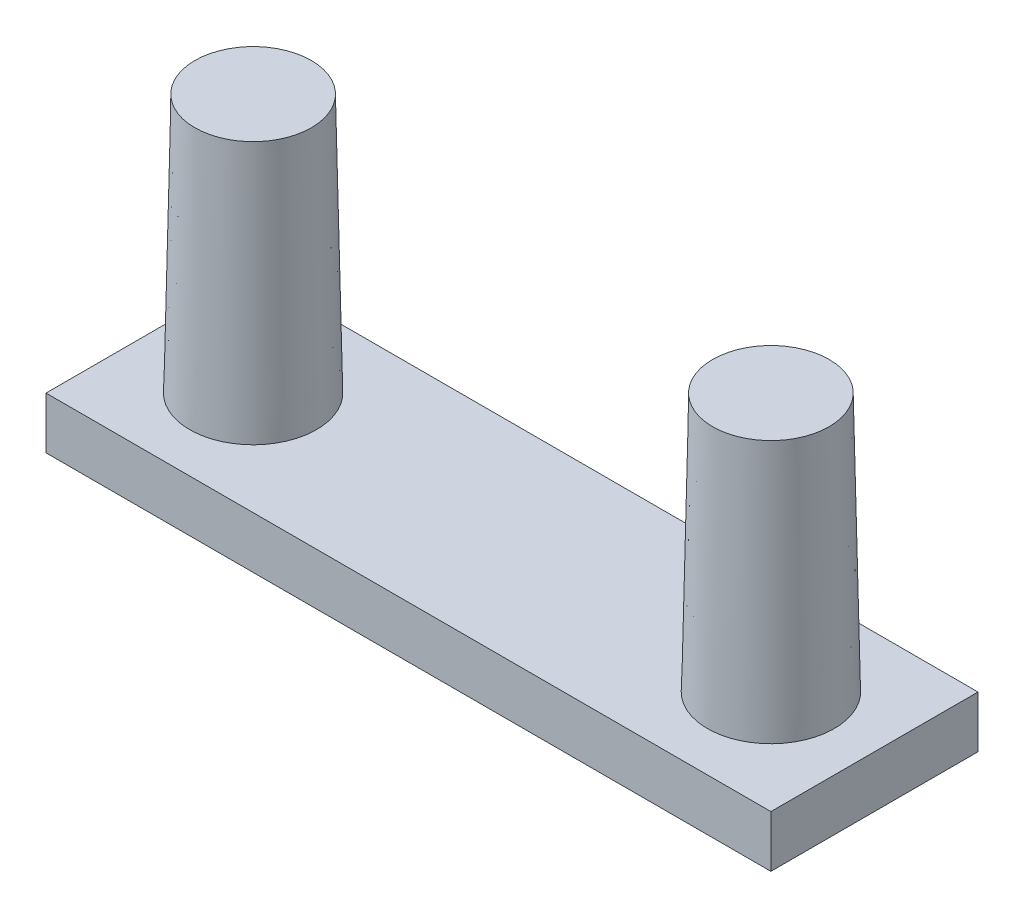
SolidWorks part; units mm, degrees
ref_plane "Front Plane" through (0, 0, 0) normal (0, 0, 1) x (1, 0, 0)
ref_plane "Top Plane" through (0, 0, 0) normal (0, 1, 0) x (1, 0, 0)
ref_plane "Right Plane" through (0, 0, 0) normal (1, 0, 0) x (0, 0, -1)
sketch "Sketch2" plane through (0, 0, 0) normal (0, 1, 0) x (1, 0, 0)
  line L1 (-14, -4) -> (14, -4)
  line L2 (-14, -4) -> (-14, 4)
  line L3 (-14, 4) -> (14, 4)
  line L4 (14, -4) -> (14, 4)
  line L5 (-14, -4) -> (14, 4) construction
  line L6 (-14, 4) -> (14, -4) construction
  point P0 (0, 0)
  dimension "D1" = 28
  dimension "D2" = 8
extrude "Boss-Extrude1" add sketch "Sketch2" along normal blind 2
sketch "Sketch3" plane through (0, 2, 0) normal (0, 1, 0) x (1, 0, 0)
  line L0 (0, 0) -> (10, 0)
  line L1 (0, 4) -> (0, -4) construction
  line L2 (14, 4) -> (-14, 4) construction
  line L3 (-14, -4) -> (14, -4) construction
  circle A0 centre (10, 0) radius 2.45
  dimension "D2" = 4.9
  dimension "D1" = 10
extrude "Boss-Extrude2" add sketch "Sketch3" along normal blind 10 contours A0 region at (10, 2, 2.3807)
chamfer "Chamfer1" distance 10 distance2 0.2 1 edges at (10, 12, 2.45) first distance on face at (10, 12, 2.45)
pattern_linear "LPattern1" count 2 spacing 20 along (-1, 0, 0) of "Boss-Extrude2", "Chamfer1"
